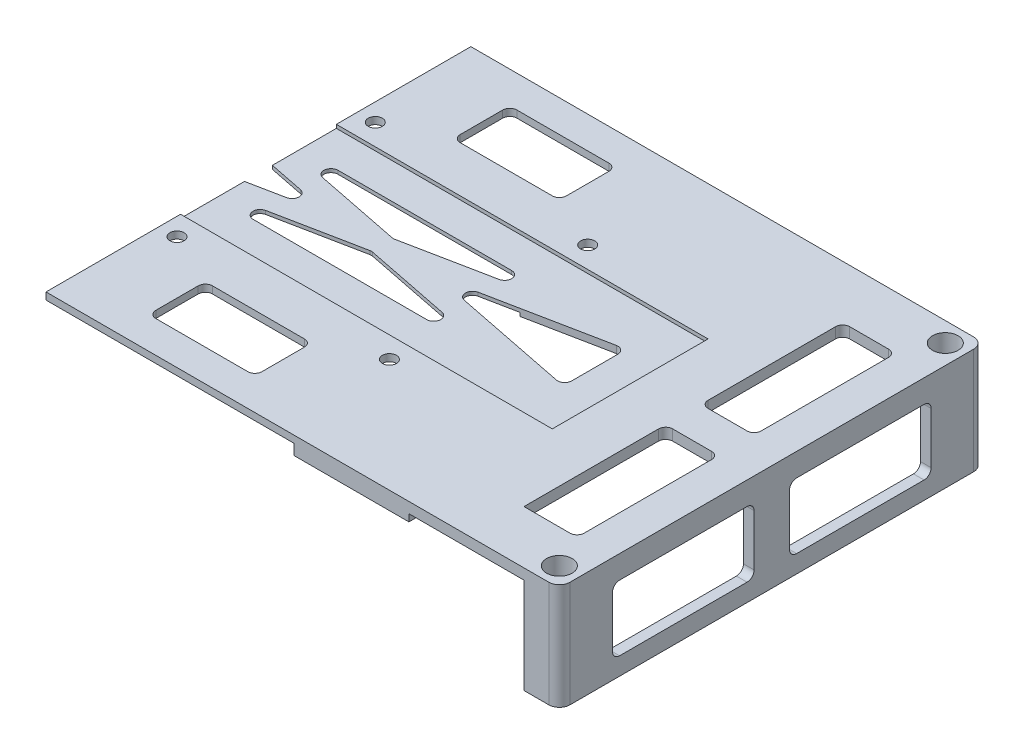
SolidWorks part; units mm, degrees
material "ABS"
ref_plane "前基準面" through (0, 0, 0) normal (0, 0, 1) x (1, 0, 0)
ref_plane "上基準面" through (0, 0, 0) normal (0, 1, 0) x (1, 0, 0)
ref_plane "右基準面" through (0, 0, 0) normal (1, 0, 0) x (0, 0, -1)
sketch "草圖8" plane through (0, 0, 0) normal (0, 1, 0) x (1, 0, 0)
  line L1 (-110, 60) -> (110, 60)
  line L2 (-110, 60) -> (-110, -60)
  line L3 (-110, -60) -> (110, -60)
  line L4 (110, 60) -> (110, -60)
extrude "填料-伸長6" add sketch "草圖8" along normal blind 3
sketch "草圖10" plane through (0, 0, 0) normal (0, -1, 0) x (1, 0, 0)
  line L1 (-110, 60) -> (-100, 60)
  line L2 (-110, 60) -> (-110, -60)
  line L3 (-110, -60) -> (-100, -60)
  line L4 (-100, 60) -> (-100, -60)
  line L5 (0, 0) -> (0, 67.9588) construction
  line L6 (0, 0) -> (59.8785, 0) construction
  line L7 (110, -60) -> (100, -60)
  line L8 (100, 60) -> (100, -60)
  line L9 (110, 60) -> (100, 60)
  line L10 (110, 60) -> (110, -60)
  dimension "D2" = 10
extrude "填料-伸長7" add sketch "草圖10" along normal blind 27
sketch "草圖9" plane through (0, 0, 0) normal (0, 1, 0) x (1, 0, 0)
  line L0 (-1000, 0) -> (49000, 0) construction
  line L1 (0, -994.7968) -> (0, 49005.2032) construction
  line L2 (110, 60) -> (-110, 60) construction
  line L4 (110, -60) -> (110, 60) construction
  circle A0 centre (104.5, 54.5) radius 2.05
  circle A1 centre (-104.5, 54.5) radius 2.05
  circle A2 centre (-104.5, -54.5) radius 2.05
  circle A3 centre (104.5, -54.5) radius 2.05
  circle A6 centre (30, 28) radius 2
  circle A7 centre (-30, 28) radius 2
  circle A8 centre (30, -28) radius 2
  circle A9 centre (-30, -28) radius 2
  dimension "D1" = 4.1
  dimension "D5" = 4
  dimension "D2" = 5.5
  dimension "D3" = 5.5
  dimension "D6" = 30
  dimension "D7" = 28
extrude "除料-伸長1" cut sketch "草圖9" against normal through all and the other way through all contours A1 | A2 | A0 | A3
sketch "草圖11" plane through (0, 3, 0) normal (0, 1, 0) x (1, 0, 0)
  line L0 (0.0013, 21.2615) -> (0.0013, 0) construction
  line L1 (0.0013, 0) -> (-26.9987, 0) construction
  line L2 (110, -60) -> (110, 60) construction
  line L3 (110, 60) -> (-110, 60) construction
  circle A0 centre (-104.4974, 54.5) radius 3.6
  circle A1 centre (-104.4974, -54.5) radius 3.6
  circle A2 centre (104.5, -54.5) radius 3.6
  circle A3 centre (104.5, 54.5) radius 3.6
  dimension "D1" = 7.2
  dimension "D2" = 5.5
  dimension "D4" = 5.5
extrude "除料-伸長2" cut sketch "草圖11" against normal blind 22 contours A1 | A0 | A3 | A2
sketch "草圖13" plane through (0, 0, 0) normal (1, 0, 0) x (0, 0, -1)
  line L0 (0, 0) -> (0, -20.0336) construction
  line L2 (-45, -3.5) -> (-5, -3.5)
  line L3 (-45, -3.5) -> (-45, -22)
  line L4 (-45, -22) -> (-5, -22)
  line L5 (-5, -3.5) -> (-5, -22)
  line L6 (60, -27) -> (-60, -27) construction
  line L8 (45, -3.5) -> (45, -22)
  line L9 (5, -3.5) -> (5, -22)
  line L10 (45, -22) -> (5, -22)
  line L11 (45, -3.5) -> (5, -3.5)
  line L12 (-60, 3) -> (-60, -27) construction
  dimension "D1" = 18.5
  dimension "D2" = 5
  dimension "D3" = 15
  dimension "D4" = 10
extrude "除料-伸長4" cut sketch "草圖13" against normal through all both and the other way through all
sketch "草圖14" plane through (0, 3, 0) normal (0, 1, 0) x (1, 0, 0)
  line L0 (0, 0) -> (-46.215, 0) construction
  line L1 (0, 0) -> (0, 32.6806) construction
  line L3 (-70, -22) -> (70, -22)
  line L4 (-70, -22) -> (-70, 22)
  line L5 (-70, 22) -> (70, 22)
  line L6 (70, -22) -> (70, 22)
  line L7 (-70, -22) -> (70, 22) construction
  line L8 (-70, 22) -> (70, -22) construction
  dimension "D1" = 140
  dimension "D2" = 44
extrude "除料-伸長7" cut sketch "草圖14" against normal blind 1
sketch "草圖15" plane through (0, 3, 0) normal (0, 1, 0) x (1, 0, 0)
  line L0 (0, 0) -> (27.6246, 0) construction
  line L1 (-100, 40) -> (-85, 40)
  line L2 (-100, 40) -> (-100, -40)
  line L3 (-100, -40) -> (-85, -40)
  line L4 (-85, 40) -> (-85, -40)
  line L5 (0, 0) -> (0, 35.214) construction
  line L6 (100, 5) -> (85, 5)
  line L7 (85, 45) -> (85, 5)
  line L8 (100, 45) -> (85, 45)
  line L9 (100, 45) -> (100, 5)
  line L10 (70, 22) -> (-70, 22) construction
  line L11 (-44.7029, -12) -> (44.7029, -12)
  line L12 (-60, -8.9406) -> (-60, 8.9406)
  line L13 (-44.7029, 12) -> (44.7029, 12)
  line L14 (60, -8.9406) -> (60, 8.9406)
  line L15 (-15, -35) -> (15, -35)
  line L16 (0, -3.0594) -> (44.7029, -12)
  line L17 (-70, 22) -> (-70, -22) construction
  line L18 (-60, 8.9406) -> (-15.2971, 0)
  line L19 (-44.7029, -12) -> (0, -3.0594)
  line L20 (-44.7029, 12) -> (0, 3.0594)
  line L21 (-60, -8.9406) -> (-15.2971, 0)
  line L22 (-15, 51) -> (15, 51)
  line L23 (-15, 51) -> (-15, 35)
  line L24 (-15, 35) -> (15, 35)
  line L25 (15, 51) -> (15, 35)
  line L26 (15, -51) -> (15, -35)
  line L27 (-15, -51) -> (15, -51)
  line L28 (15.2971, 0) -> (60, -8.9406)
  line L29 (0, 3.0594) -> (44.7029, 12)
  line L30 (15.2971, 0) -> (60, 8.9406)
  line L31 (-15, -51) -> (-15, -35)
  line L32 (100, -45) -> (100, -5)
  line L33 (100, -45) -> (85, -45)
  line L34 (85, -45) -> (85, -5)
  line L35 (100, -5) -> (85, -5)
  line L36 (110, 60) -> (-110, 60) construction
  dimension "D1" = 40
  dimension "D2" = 85
  dimension "D3" = 15
  dimension "D4" = 10
  dimension "D5" = 10
  dimension "D6" = 30
  dimension "D7" = 16
  dimension "D8" = 35
  dimension "D9" = 85
  dimension "D10" = 80
  dimension "D11" = 15
extrude "除料-伸長8" cut sketch "草圖15" against normal through all
extrude "除料-伸長9" cut sketch "草圖9<5>" along normal through all contours A7 | A6 | A9 | A8
sketch "草圖9<5>" plane through (0, 0, 0) normal (0, 1, 0) x (1, 0, 0) same geometry as "草圖9"
sketch "草圖19" plane through (0, -27, 0) normal (0, -1, 0) x (1, 0, 0)
  line L5 (0, -57.1205) -> (0, 57.1205) construction
  line L6 (0, 0) -> (-76.5655, 0) construction
  line L12 (-100, 54.5) -> (-100, -54.5)
  line L15 (-110, 60) -> (-110, -60) construction
  line L16 (-104.5, 50) -> (-107, 50)
  line L18 (-104.5, -50) -> (-107, -50)
  line L19 (-107, 50) -> (-107, -50)
  line L20 (100, 54.5) -> (100, -54.5)
  line L21 (104.5, -50) -> (107, -50)
  line L22 (107, 50) -> (107, -50)
  line L23 (104.5, 50) -> (107, 50)
  arc A0 (-104.5, 50) -> (-100, 54.5) centre (-104.5, 54.5) ccw
  arc A1 (-104.5, -50) -> (-100, -54.5) centre (-104.5, -54.5) cw
  arc A4 (104.5, 50) -> (100, 54.5) centre (104.5, 54.5) cw
  arc A5 (104.5, -50) -> (100, -54.5) centre (104.5, -54.5) ccw
  point P10 (0, 0)
  dimension "D2" = 9
  dimension "D1" = 3
extrude "除料-伸長13" cut sketch "草圖19" against normal blind 27
sketch "草圖20" plane through (0, 0, 0) normal (0, -1, 0) x (1, 0, 0)
  line L0 (0, 0) -> (0, 103.9697) construction
  line L1 (0, 0) -> (143.2508, 0) construction
  line L2 (-100, 60) -> (100, 60) construction
  line L3 (-67.5, 60) -> (67.5, 60)
  line L4 (-67.5, 60) -> (-67.5, 52)
  line L5 (-67.5, 52) -> (67.5, 52)
  line L6 (67.5, 60) -> (67.5, 52)
  line L7 (-67.5, -52) -> (67.5, -52)
  line L8 (67.5, -60) -> (67.5, -52)
  line L9 (-67.5, -60) -> (67.5, -60)
  line L10 (-67.5, -60) -> (-67.5, -52)
  line L12 (-59, 32.5) -> (-39, 32.5)
  line L13 (-59, 32.5) -> (-59, 25)
  line L14 (-59, 25) -> (-54, 25)
  line L15 (-39, 32.5) -> (-39, 29.5)
  line L28 (-85, 40) -> (-85, -40) construction
  line L31 (-54, 25) -> (-54, 29.5)
  line L32 (-54, 29.5) -> (-39, 29.5)
  line L33 (54, 29.5) -> (39, 29.5)
  line L34 (54, 25) -> (54, 29.5)
  line L35 (39, 32.5) -> (39, 29.5)
  line L36 (59, 25) -> (54, 25)
  line L37 (59, 32.5) -> (59, 25)
  line L38 (59, 32.5) -> (39, 32.5)
  line L39 (59, -32.5) -> (39, -32.5)
  line L40 (59, -32.5) -> (59, -25)
  line L41 (59, -25) -> (54, -25)
  line L42 (39, -32.5) -> (39, -29.5)
  line L43 (54, -25) -> (54, -29.5)
  line L44 (54, -29.5) -> (39, -29.5)
  line L45 (-54, -29.5) -> (-39, -29.5)
  line L46 (-54, -25) -> (-54, -29.5)
  line L47 (-39, -32.5) -> (-39, -29.5)
  line L48 (-59, -25) -> (-54, -25)
  line L49 (-59, -32.5) -> (-59, -25)
  line L50 (-59, -32.5) -> (-39, -32.5)
  dimension "D1" = 135
  dimension "D2" = 8
  dimension "D3" = 20
  dimension "D4" = 7.5
  dimension "D5" = 26
  dimension "D6" = 25
  dimension "D7" = 3
  dimension "D8" = 5
extrude "填料-伸長8" add sketch "草圖20" along normal blind 2
fillet "圓角1" radius 3 4 edges at (-110, -12, 60) (-110, -12, -60) (110, -12, -60) (110, -12, 60)
fillet "圓角2" radius 2 49 edges at (-107, 0, 0) (107, 0, 0) (108.5, -3.5, -5) (108.5, -3.5, 45) (108.5, -22, 45) (108.5, -22, -5) (108.5, -3.5, -45) (108.5, -3.5, 5) (108.5, -22, 5) (108.5, -22, -45) (-108.5, -22, -45) (-108.5, -22, 5) (-108.5, -3.5, -45) (-108.5, -3.5, 5) (-108.5, -22, 45) (-108.5, -3.5, 45) (-108.5, -3.5, -5) (-108.5, -22, -5) (60, 1, -8.9406) (44.7029, 1, -12) (-44.7029, 1, -12) (0, 1, 3.0594) (-44.7029, 1, 12) (44.7029, 1, 12) (-15.2971, 1, 0) (0, 1, -3.0594) (60, 1, 8.9406) (100, 1.5, -5) (15, 1.5, -35) (100, 1.5, 45) (15, 1.5, 51) (-85, 1.5, 40) (-15, 1.5, 51) (85, 1.5, -5) (15.2971, 1, 0) (-100, 1.5, 40) (-15, 1.5, -35) (-60, 1, 8.9406) (-60, 1, -8.9406) (15, 1.5, 35) (-15, 1.5, 35) (85, 1.5, 5) (85, 1.5, -45) (100, 1.5, 5) (100, 1.5, -45) (15, 1.5, -51) (-15, 1.5, -51) (-85, 1.5, -40) (-100, 1.5, -40)
sketch "草圖21" plane through (0, 0, 0) normal (0, 0, 1) x (1, 0, 0)
  line L0 (0, 0) -> (0, 39.2806) construction
  line L4 (-35, 3) -> (-35, 1)
  line L7 (-35, 1) -> (35, 1)
  line L8 (35, -27) -> (35, 1)
  line L9 (-35, 3) -> (-110, 3)
  line L10 (-110, 3) -> (-110, -27)
  line L11 (-110, -27) -> (35, -27)
  point P10 (110, -27)
  dimension "D1" = 2
  dimension "D2" = 70
  dimension "D3" = 35
extrude "除料-伸長14" cut sketch "草圖21" against normal through all both and the other way through all
